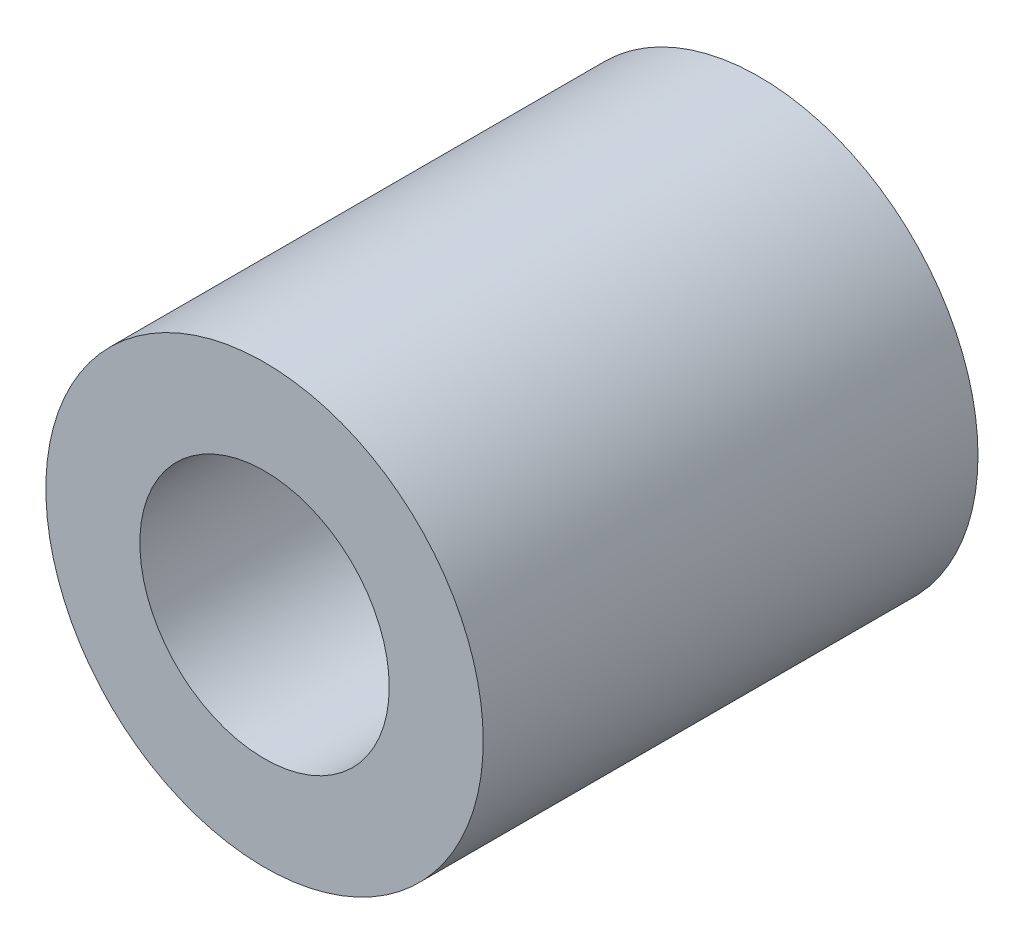
SolidWorks part; units mm, degrees
ref_plane "Front Plane" through (0, 0, 0) normal (0, 0, 1) x (1, 0, 0)
ref_plane "Top Plane" through (0, 0, 0) normal (0, 1, 0) x (1, 0, 0)
ref_plane "Right Plane" through (0, 0, 0) normal (1, 0, 0) x (0, 0, -1)
sketch "Sketch1" plane through (0, 0, 0) normal (0, 0, 1) x (1, 0, 0)
  circle A0 centre (0, 0) radius 2.8067
  circle A1 centre (0, 0) radius 1.6002
  dimension "OD" = 5.6134
  dimension "ID" = 3.2004
sketch "Sketch2" plane through (0, 0, 0) normal (1, 0, 0) x (0, 0, -1)
  line L2 (3.175, 0) -> (-3.175, 0) construction
  line L4 (-3.175, -2.8067) -> (-3.175, 2.8067) construction
  line L5 (-3.175, -1.6002) -> (3.175, -1.6002)
  line L6 (3.175, 1.6002) -> (-3.175, 1.6002)
  line L7 (3.175, -2.8067) -> (3.175, 2.8067) construction
  line L8 (-3.175, 2.8067) -> (3.175, 2.8067) construction
  line L9 (-3.175, -2.8067) -> (3.175, -2.8067) construction
  line L10 (0, 2.8067) -> (0, -2.8067) construction
  line L11 (0, 1.6002) -> (0, -1.6002) construction
  point P4 (0, -1.6002)
  point P7 (0, 1.6002)
  point P8 (0, 0)
  point P12 (-3.175, 0)
  point P15 (3.175, 0)
  point P16 (0, -2.8067)
  point P17 (0, 2.8067)
  dimension "Length" = 6.35
sketch "Sketch5" plane through (0, 0, 0) normal (0, 0, 1) x (1, 0, 0)
  circle A1 centre (0, 0) radius 1.6002
  circle A2 centre (0, 0) radius 1.6002
  circle A3 centre (0, 0) radius 2.8067
  circle A4 centre (0, 0) radius 2.8067
  dimension "D1" = 0
  dimension "D2" = 0
extrude "Boss-Extrude1" add sketch "Sketch5" along normal up to vertex and the other way up to vertex up to point (0, 0, 3.175) other way up to point (0, 0, -3.175)
sketch "Sketch4" plane through (0, 0, 3.175) normal (0, 0, 1) x (1, 0, 0)
  line L0 (0, 0) -> (-1.1315, 1.1315)
  line L2 (0, -2.8067) -> (0, 2.8067) construction
  circle A1 centre (0, 0) radius 1.6002 construction
  dimension "D1" = 45
equation "\"D1\"= \"Length@Sketch2\""
